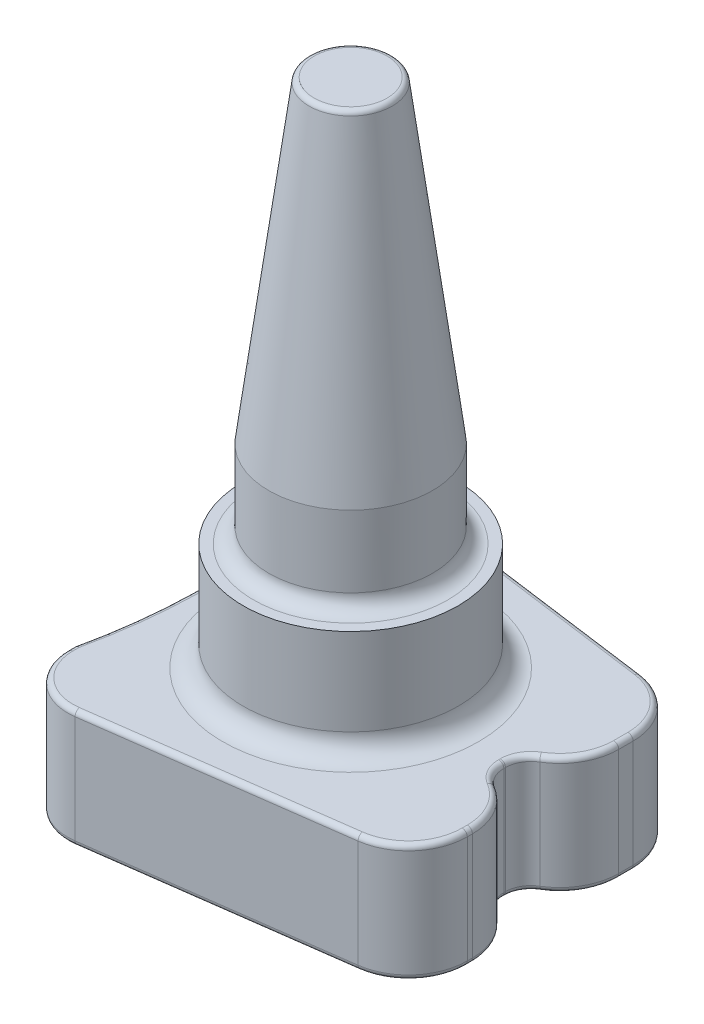
SolidWorks part; units mm, degrees
ref_plane "Plano frontal" through (0, 0, 0) normal (0, 0, 1) x (1, 0, 0)
ref_plane "Plano superior" through (0, 0, 0) normal (0, 1, 0) x (1, 0, 0)
ref_plane "Plano direito" through (0, 0, 0) normal (1, 0, 0) x (0, 0, -1)
sketch "Esboço1" plane through (0, 0, 0) normal (0, 0, 1) x (1, 0, 0)
  line L0 (17.3846, 86.7357) -> (17.3846, -75.0236) construction
  line L1 (17.3846, 86.7357) -> (25.3846, 86.7357)
  line L2 (25.3846, 86.7357) -> (33.3846, 24.7357)
  line L3 (33.3846, 24.7357) -> (33.3846, 7.7357)
  line L4 (33.3846, 7.7357) -> (38.3846, 7.7357)
  line L5 (38.3846, 7.7357) -> (38.3846, -13.2643)
  line L6 (38.3846, -13.2643) -> (97.3846, -13.2643)
  line L7 (97.3846, -13.2643) -> (97.3846, -36.2643)
  line L8 (97.3846, -36.2643) -> (17.3846, -36.2643)
  line L9 (17.3846, 86.7357) -> (17.3846, -36.2643)
  dimension "D1" = 8
  dimension "D2" = 80
  dimension "D3" = 21
  dimension "D4" = 16
  dimension "D5" = 23
  dimension "D6" = 44
  dimension "D7" = 61
  dimension "D8" = 123
revolve "Revolução1" add sketch "Esboço1" angle 360 about L0
sketch "Esboço2" plane through (0, -36.2643, 0) normal (0, -1, 0) x (1, 0, 0)
  line L0 (-62.6154, 0) -> (17.3846, 0) construction
  line L1 (56.3846, 26.25) -> (56.3846, -26.25)
  line L2 (-13.6154, 0) -> (17.3846, 0) construction
  line L3 (-13.6154, 35.75) -> (-13.6154, -35.75)
  line L4 (-13.6154, 35.75) -> (56.3846, 26.25)
  line L5 (-13.6154, -35.75) -> (56.3846, -26.25)
  circle A0 centre (17.3846, 0) radius 80 construction
  dimension "D1" = 52.5
  dimension "D2" = 31
  dimension "D3" = 71.5
extrude "Corte-extrusão2" cut sketch "Esboço2" against normal through all flip side to cut
sketch "Esboço3" plane through (0, -36.2643, 0) normal (0, -1, 0) x (1, 0, 0)
  line L0 (-13.6154, 0) -> (-117.6154, 0) construction
  line L1 (-13.6154, 35.75) -> (-13.6154, -35.75) construction
  line L2 (-13.6154, 0) -> (-11.1154, 0) construction
  circle A0 centre (-117.6154, 0) radius 106.5
  dimension "D1" = 2.5
  dimension "D2" = 104
extrude "Corte-extrusão3" cut sketch "Esboço3" against normal through all
fillet "Filete1" radius 10 2 edges at (-13.6154, -24.7643, -35.75) (-13.6154, -24.7643, 35.75)
sketch "Esboço4" plane through (0, -36.2643, 0) normal (0, -1, 0) x (1, 0, 0)
  line L0 (56.3846, -4.25) -> (48.3846, -4.25)
  line L1 (56.3846, -26.25) -> (56.3846, 26.25) construction
  line L2 (56.3846, 4.25) -> (48.3846, 4.25)
  line L3 (-11.1154, 0) -> (75.7968, 0) construction
  line L4 (48.3846, 4.25) -> (48.3846, -4.25)
  line L5 (48.3846, -4.25) -> (48.384, -4.0765)
  line L6 (56.3846, 4.25) -> (56.3846, -4.25)
  arc A0 (-13.6154, -22.9401) -> (-13.6154, 22.9401) centre (-117.6154, 0) ccw construction
  line M4 (56.3846, -26.25) -> (56.3846, 26.25)
  dimension "D2" = 8
extrude "Corte-extrusão4" cut sketch "Esboço4" against normal through all contours L4 L3 L6 L2 | L3 L4 L0 M4 region at (52.3846, -36.2643, -2.125) region at (52.3846, -36.2643, 2.125)
fillet "Filete2" radius 11.5 1 edges at (56.3846, -24.7643, 26.25)
fillet "Filete3" radius 11.5 1 edges at (56.3846, -24.7643, 4.25)
fillet "Filete4" radius 5 1 edges at (48.3846, -24.7643, 4.25)
fillet "Filete5" radius 5 1 edges at (48.3846, -24.7643, -4.25)
fillet "Filete6" radius 11.5 2 edges at (56.3846, -24.7643, -26.25) (56.3846, -24.7643, -4.25)
fillet "Filete7" radius 4 1 edges at (-3.6154, -13.2643, 0)
fillet "Filete8" radius 3 1 edges at (1.3846, 7.7357, 0)
fillet "Filete9" radius 1 17 edges at (9.3846, 86.7357, 0) (-13.6154, -13.2643, 23.6207) (-13.6154, -13.2643, -23.6207) (-10.1938, -13.2643, -31.8327) (-11.1154, -13.2643, 0) (-10.1938, -13.2643, 31.8327) (22.0803, -13.2643, 30.9056) (48.3846, -13.2643, 0.9062) (56.3846, -13.2643, 15.7049) (53.5459, -13.2643, 23.7705) (54.8941, -13.2643, 9.5422) (49.0327, -13.2643, 3.5241) (49.0327, -13.2643, -1.7118) (56.3846, -13.2643, -14.7987) (54.8941, -13.2643, -7.7299) (53.5459, -13.2643, -23.7705) (22.0803, -13.2643, -30.9056)
fillet "Filete10" radius 1 16 edges at (-10.1938, -36.2643, -31.8327) (-13.6154, -36.2643, -23.6207) (-11.1154, -36.2643, 0) (-13.6154, -36.2643, 23.6207) (-10.1938, -36.2643, 31.8327) (22.0803, -36.2643, 30.9056) (53.5459, -36.2643, 23.7705) (56.3846, -36.2643, 15.7049) (54.8941, -36.2643, 9.5422) (49.0327, -36.2643, 3.5241) (48.3846, -36.2643, 0.9062) (49.0327, -36.2643, -1.7118) (54.8941, -36.2643, -7.7299) (56.3846, -36.2643, -14.7987) (53.5459, -36.2643, -23.7705) (22.0803, -36.2643, -30.9056)
sketch "Esboço5" plane through (0, -36.2643, 0) normal (0, -1, 0) x (1, 0, 0)
  line L0 (-10.1154, 0) -> (47.3846, 0.75) construction
  arc A0 (-12.6154, -23.0489) -> (-12.6154, 23.0489) centre (-117.6154, 0) ccw construction
  circle A1 centre (18.6346, 0.375) radius 20.5
  dimension "D1" = 41
extrude "Corte-extrusão6" cut sketch "Esboço5" against normal blind 2.5
chamfer "Chanfro1" distance 2 angle 45 1 edges at (39.1346, -33.7643, 0.375)
sketch "Esboço6" plane through (0, -33.7643, 0) normal (0, -1, 0) x (1, 0, 0)
  line L0 (0, 0) -> (18.6346, 0.375) construction
  line L1 (13.6346, 10.375) -> (23.6346, -9.625) construction
  line L2 (13.6346, 10.375) -> (23.6346, 10.375)
  line L3 (13.6346, 10.375) -> (13.6346, -9.625)
  line L4 (13.6346, -9.625) -> (23.6346, -9.625)
  line L5 (23.6346, 10.375) -> (23.6346, -9.625)
  dimension "D1" = 10
  dimension "D2" = 20
extrude "Corte-extrusão7" cut sketch "Esboço6" against normal blind 10
chamfer "Chanfro2" distance 1 angle 45 4 edges at (18.6346, -33.7643, -9.625) (23.6346, -33.7643, 0.375) (13.6346, -33.7643, 0.375) (18.6346, -33.7643, 10.375)
